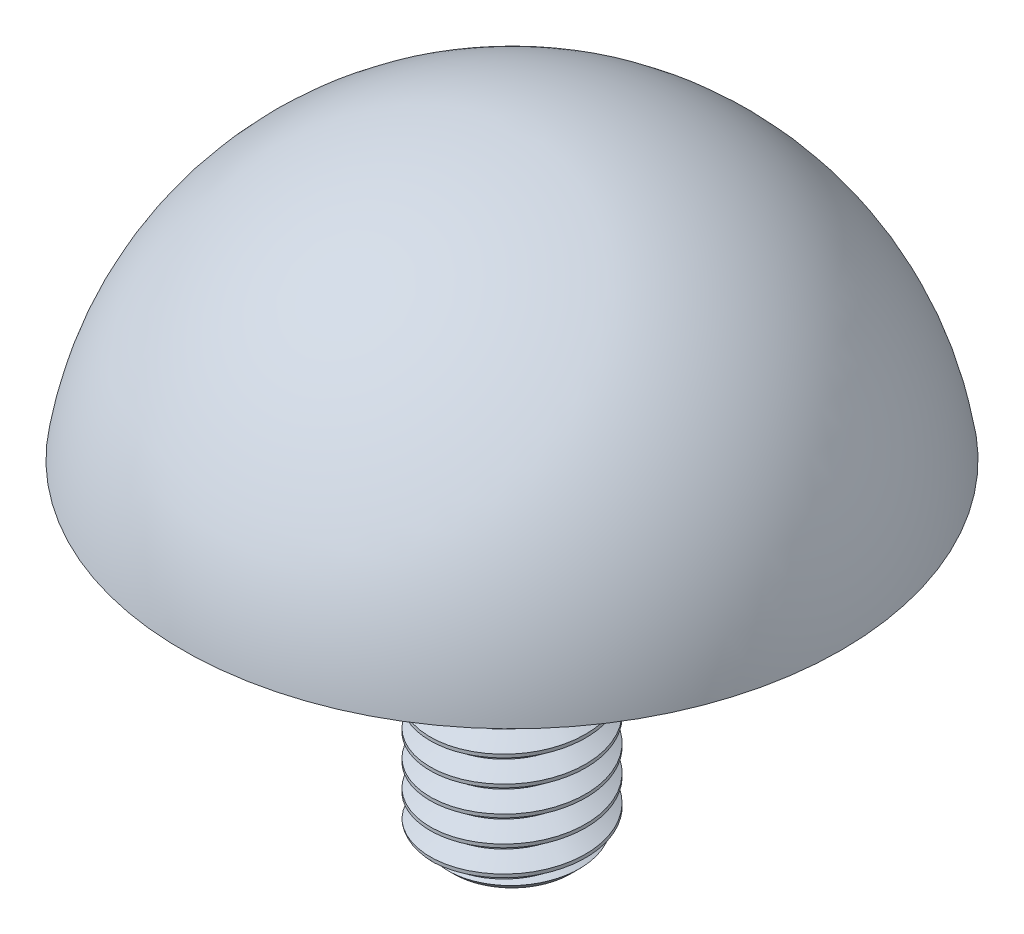
SolidWorks part; units mm, degrees
ref_plane "Front Plane" through (0, 0, 0) normal (0, 0, 1) x (1, 0, 0)
ref_plane "Top Plane" through (0, 0, 0) normal (0, 1, 0) x (1, 0, 0)
ref_plane "Right Plane" through (0, 0, 0) normal (1, 0, 0) x (0, 0, -1)
sketch "Sketch1" plane through (0, 0, 0) normal (0, 0, 1) x (1, 0, 0)
  line L0 (0, 0) -> (0, 10.922) construction
  line L1 (0, 0) -> (0, -12.7) construction
  line L2 (-12.7, 0) -> (12.7, 0) construction
  line L3 (3, -12.7) -> (-3, -12.7) construction
  line L4 (3.1083, -12.6375) -> (2.2422, -13.1375) construction
  line L5 (2.2422, -13.1375) -> (3.1083, -13.6375) construction
  line L6 (3.1083, -13.6375) -> (3.1083, -12.6375) construction
  line L7 (3, -12.7) -> (3, -13.575) construction
  line L8 (3.1083, -13.1375) -> (3, -13.1375) construction
  line L9 (3, -13.1375) -> (2.3505, -13.1375) construction
  line L10 (2.3505, -13.1375) -> (2.2422, -13.1375) construction
  line L11 (2.3505, -13.075) -> (2.3505, -13.2)
  line L12 (3.0541, -12.6688) -> (3.0541, -13.6062)
  line L13 (2.3505, -13.2) -> (3.0541, -13.6062)
  line L14 (2.3505, -13.075) -> (3.0541, -12.6688)
  point P7 (0, 0)
  point P10 (0, -12.7)
  point P22 (3.0541, -13.1375)
  point P24 (3, -10.7)
  dimension "OD" = 25.4
  dimension "Height" = 10.922
  dimension "Thread Length" = 12.7
  dimension "Thread Size" = 6
  dimension "Pitch" = 1
  dimension "D2" = 0.125
  dimension "D1" = 2
sketch "Sketch2" plane through (0, 0, 0) normal (0, 0, 1) x (1, 0, 0)
  line L0 (0, -12.7) -> (0, 10.922)
  line L3 (12.7, 0) -> (3, 0)
  line L4 (-12.7, 0) -> (12.7, 0) construction
  line L5 (3, 0) -> (3, -12.7)
  line L6 (3, -12.7) -> (0, -12.7)
  arc A2 (12.7, 0) -> (0, 10.922) centre (0, -1.9227) ccw
revolve "Revolve1" add sketch "Sketch2" angle 360 about L0
sketch "Sketch3" plane through (0, -12.7, 0) normal (0, -1, 0) x (1, 0, 0)
  circle A0 centre (0, 0) radius 3 construction
  circle A1 centre (0, 0) radius 3
curve "Helix/Spiral1" pitch 1 height 13.7 radius 3 centre (0, -12.7, 0) axis (0, 1, 0) start towards (1, 0, 0) parameters "Pitch"=1
sketch "Sketch4" plane through (0, 0, 0) normal (0, 0, 1) x (1, 0, 0)
  line L4 (2.3505, -13.075) -> (2.3505, -13.2) construction
  line L5 (2.3505, -13.075) -> (3.0541, -12.6688) construction
  line L6 (3.0541, -12.6688) -> (3.0541, -13.6062) construction
  line L7 (2.3505, -13.2) -> (3.0541, -13.6062) construction
  line L8 (2.3505, -13.075) -> (2.3505, -13.2)
  line L9 (2.3505, -13.075) -> (3.0541, -12.6688)
  line L10 (3.0541, -12.6688) -> (3.0541, -13.6062)
  line L11 (2.3505, -13.2) -> (3.0541, -13.6062)
chamfer "Chamfer1" distance 0.75 angle 45 1 edges at (3, -12.7, 0)
sweep "Cut-Sweep1" cut profiles "Sketch4" path "Helix/Spiral1"
equation "\"D3@Helix/Spiral1\"=\"Thread Length@Sketch1\"+\"Pitch@Helix/Spiral1\""
equation "\"D1@Chamfer1\"=\"Pitch@Helix/Spiral1\"*.75"
equation "\"D2@Sketch1\" = \"Pitch@Sketch1\" / 8"
equation "\"D1@Sketch1\"=\"Pitch@Sketch1\"*2"
equation "\"Pitch@Helix/Spiral1\"=\"pitch@sketch1\""
